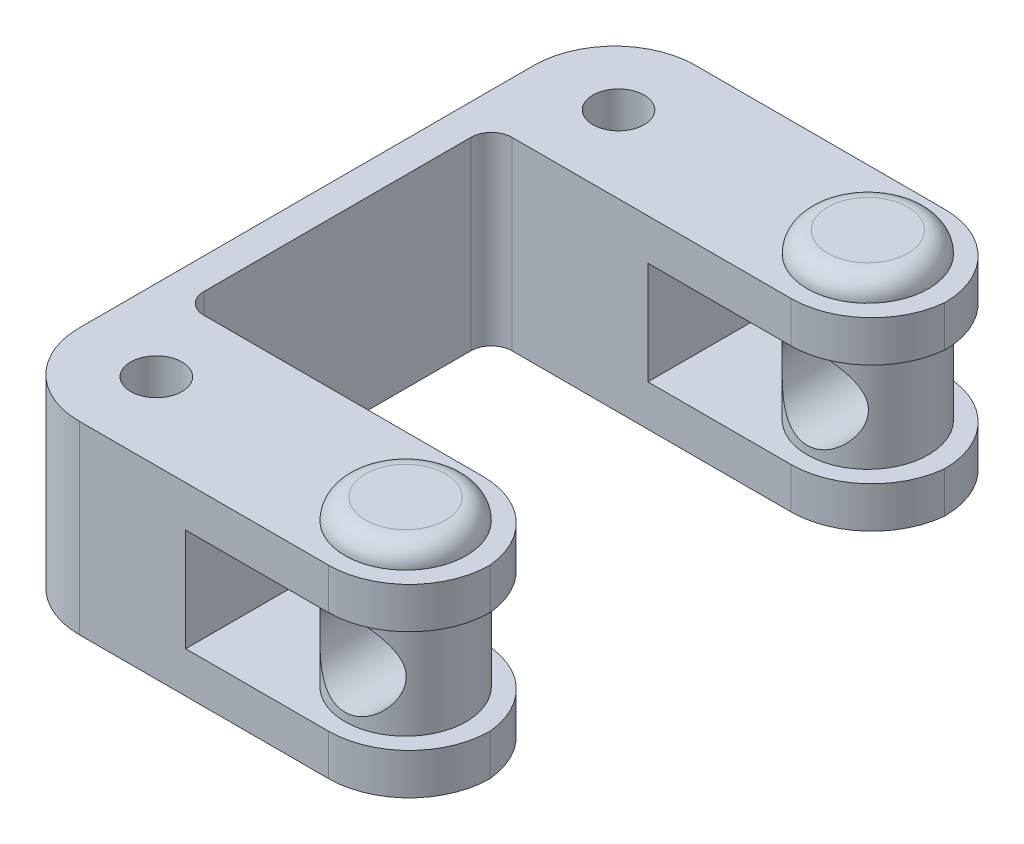
SolidWorks part; units mm, degrees
ref_plane "Front Plane" through (0, 0, 0) normal (0, 0, 1) x (1, 0, 0)
ref_plane "Top Plane" through (0, 0, 0) normal (0, 1, 0) x (1, 0, 0)
ref_plane "Right Plane" through (0, 0, 0) normal (1, 0, 0) x (0, 0, -1)
sketch "Sketch7" plane through (0, 0, 0) normal (0, 0, 1) x (1, 0, 0)
  line L1 (-47.8245, -17.2167) -> (2.9755, -17.2167)
  line L2 (-47.8245, -17.2167) -> (-47.8245, -22.2967)
  line L3 (-24.6692, -22.2967) -> (2.9755, -22.2967)
  line L4 (2.9755, -17.2167) -> (2.9755, -22.2967)
  line L6 (-47.8245, -22.2967) -> (-47.8245, -34.9967)
  line L8 (-24.6692, -22.2967) -> (-24.6692, -34.9967)
  line L9 (-24.6692, -34.9967) -> (2.9755, -34.9967)
  line L10 (-47.8245, -34.9967) -> (-47.8245, -40.0767)
  line L11 (-47.8245, -40.0767) -> (2.9755, -40.0767)
  line L12 (2.9755, -34.9967) -> (2.9755, -40.0767)
  dimension "D1" = 5.08
  dimension "D2" = 5.08
  dimension "D3" = 12.7
  dimension "D4" = 50.8
extrude "Boss-Extrude4" add sketch "Sketch7" along normal blind 76.2 contours L1 L4 L3 L8 L9 L12 L11 L10 L6 L2
fillet "Fillet1" radius 10 6 edges at (-47.8245, -28.6467, 76.2) (2.9755, -37.5367, 76.2) (2.9755, -19.7567, 76.2) (-47.8245, -28.6467, 0) (2.9755, -37.5367, 0) (2.9755, -19.7567, 0)
sketch "Sketch8" plane through (0, -17.2167, 0) normal (0, 1, 0) x (1, 0, 0)
  line L0 (-22.4245, -76.2) -> (-22.4245, -57.15) construction
  line L1 (-37.8245, -76.2) -> (-7.0245, -76.2) construction
  line L2 (-22.4245, 0) -> (-22.4245, -19.05) construction
  line L3 (-37.8245, 0) -> (-7.0245, 0) construction
  line L4 (2.9755, -66.2) -> (2.9755, -10) construction
  line L5 (2.9755, -57.15) -> (-44.0145, -57.15)
  line L6 (2.9755, -57.15) -> (2.9755, -19.05)
  line L7 (2.9755, -19.05) -> (-44.0145, -19.05)
  line L8 (-44.0145, -57.15) -> (-44.0145, -19.05)
  line L9 (-47.8245, -38.1) -> (-44.0145, -38.1) construction
  line L10 (-47.8245, -66.2) -> (-47.8245, -10) construction
  dimension "D1" = 19.05
  dimension "D2" = 19.05
  dimension "D3" = 3.81
extrude "Cut-Extrude2" cut sketch "Sketch8" against normal blind 25.4
fillet "Fillet2" radius 10 4 edges at (2.9755, -37.5367, 57.15) (2.9755, -37.5367, 19.05) (2.9755, -19.7567, 19.05) (2.9755, -19.7567, 57.15)
sketch "Sketch9" plane through (0, -17.2167, 0) normal (0, 1, 0) x (1, 0, 0)
  line L0 (-7.0245, -76.2) -> (-6.9793, -57.15) construction
  line L1 (-6.9793, -19.05) -> (-7.0245, 0) construction
  circle A0 centre (-7.0019, -66.675) radius 7.493
  circle A1 centre (-7.0019, -9.525) radius 7.493
  dimension "D1" = 14.986
  dimension "D2" = 14.986
extrude "Boss-Extrude5" add sketch "Sketch9" along normal blind 2.54
fillet "Fillet4" radius 2.54 2 edges at (-7.0019, -14.6767, 17.018) (-7.0019, -14.6767, 74.168)
sketch "Sketch10" plane through (0, -34.9967, 0) normal (0, 1, 0) x (1, 0, 0)
  line L0 (-7.0245, -76.2) -> (-6.9793, -57.15) construction
  line L1 (-6.9793, -19.05) -> (-7.0245, 0) construction
  circle A0 centre (-7.0019, -66.675) radius 7.493
  circle A1 centre (-7.0019, -9.525) radius 7.493
  dimension "D1" = 14.986
  dimension "D2" = 14.986
extrude "Boss-Extrude6" add sketch "Sketch10" along normal up to next
sketch "Sketch11" plane through (0, 0, 76.2) normal (0, 0, 1) x (1, 0, 0)
  line L0 (-14.4949, -28.6467) -> (0.4911, -28.6467) construction
  line L1 (-14.4949, -22.2967) -> (-14.4949, -34.9967) construction
  line L2 (0.4911, -34.9967) -> (0.4911, -22.2967) construction
  line L3 (-7.0019, -22.2967) -> (-7.0245, -34.9967) construction
  line L4 (-14.4949, -22.2967) -> (0.4911, -22.2967) construction
  circle A0 centre (-7.0019, -28.6467) radius 5.334
  dimension "D1" = 10.668
extrude "Cut-Extrude3" cut sketch "Sketch11" against normal blind 76.2
fillet "Fillet5" radius 2.54 2 edges at (-44.0145, -28.6467, 57.15) (-44.0145, -28.6467, 19.05)
sketch "Sketch12" plane through (-47.8245, 0, 0) normal (-1, 0, 0) x (0, 0, 1)
  line L0 (10, -28.6467) -> (66.2, -28.6467) construction
  line L1 (10, -17.2167) -> (10, -40.0767) construction
  line L2 (66.2, -40.0767) -> (66.2, -17.2167) construction
  line L3 (38.1, -17.2167) -> (38.1, -36.2667) construction
  line L4 (66.2, -17.2167) -> (10, -17.2167) construction
  line L5 (66.2, -40.0767) -> (10, -40.0767) construction
  line L7 (29.21, -40.0767) -> (38.1, -40.0767)
  line L8 (29.21, -40.0767) -> (29.21, -36.2667)
  line L9 (29.21, -36.2667) -> (38.1, -36.2667)
  line L11 (38.1, -36.2667) -> (46.99, -36.2667)
  line L13 (38.1, -40.0767) -> (46.99, -40.0767)
  line L14 (46.99, -36.2667) -> (46.99, -40.0767)
  dimension "D1" = 8.89
  dimension "D2" = 3.81
  dimension "D3" = 8.89
sketch "Sketch14" plane through (0, -17.2167, 0) normal (0, 1, 0) x (1, 0, 0)
  line L0 (-37.8245, 0) -> (-37.8245, -19.05) construction
  line L1 (-6.9793, -19.05) -> (-41.4745, -19.05) construction
  line L2 (-37.8245, -57.15) -> (-37.8245, -76.2) construction
  line L3 (-41.4745, -57.15) -> (-6.9793, -57.15) construction
  circle A0 centre (-37.8245, -9.525) radius 3.175
  circle A1 centre (-37.8245, -66.675) radius 3.175
  dimension "D1" = 6.35
  dimension "D2" = 6.35
extrude "Cut-Extrude5" cut sketch "Sketch14" against normal up to next contours A0 | A1
